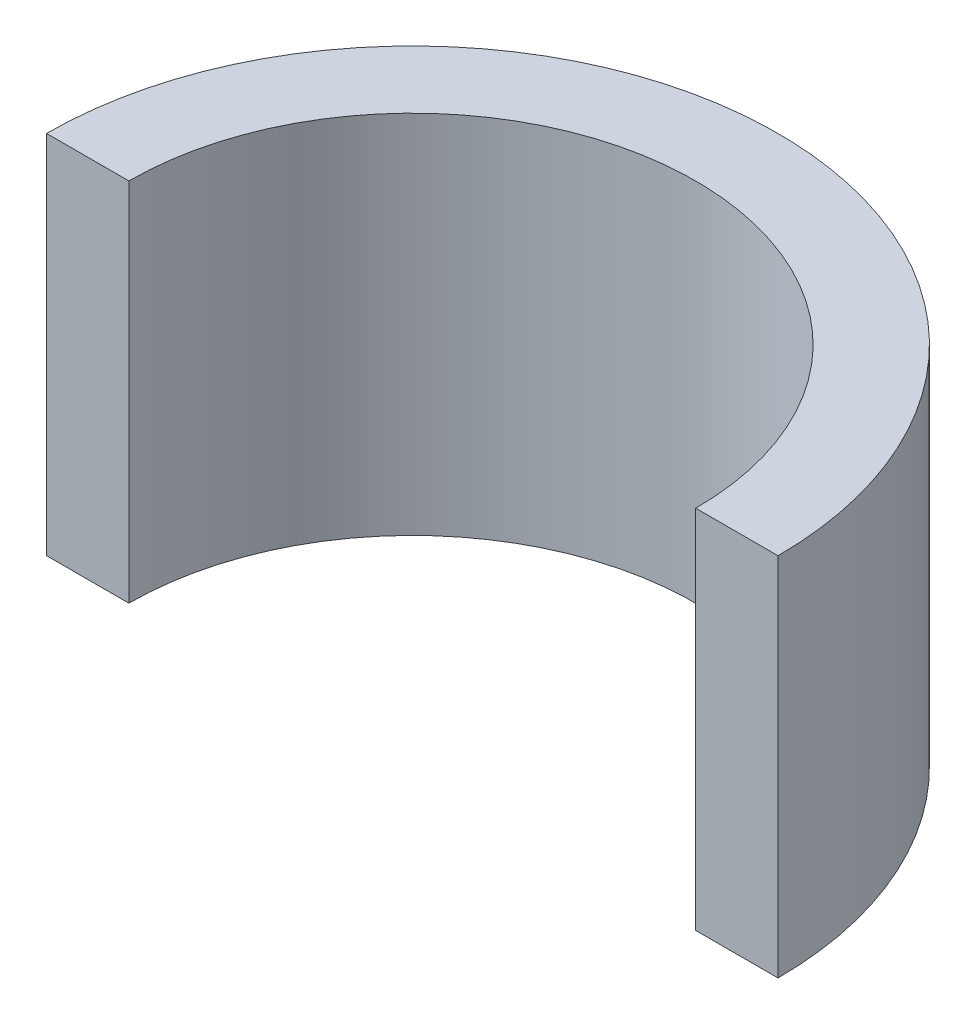
SolidWorks part; units mm, degrees
ref_plane "Front Plane" through (0, 0, 0) normal (0, 0, 1) x (1, 0, 0)
ref_plane "Top Plane" through (0, 0, 0) normal (0, 1, 0) x (1, 0, 0)
ref_plane "Right Plane" through (0, 0, 0) normal (1, 0, 0) x (0, 0, -1)
sketch "Sketch1" plane through (0, 0, 0) normal (0, 1, 0) x (1, 0, 0)
  line L0 (-7.75, 0) -> (7.75, 0)
  line L1 (-10, 0) -> (-7.75, 0)
  line L2 (7.75, 0) -> (10, 0)
  arc A0 (-7.75, 0) -> (7.75, 0) centre (0, 0) cw
  arc A1 (-10, 0) -> (10, 0) centre (0, 0) cw
  point P6 (0, 0)
  dimension "D1" = 7.75
  dimension "D2" = 10
extrude "Boss-Extrude1" add sketch "Sketch1" along normal blind 10 contours A1 L1 A0 L2 region at (-8.875, 0, -0.2236)
